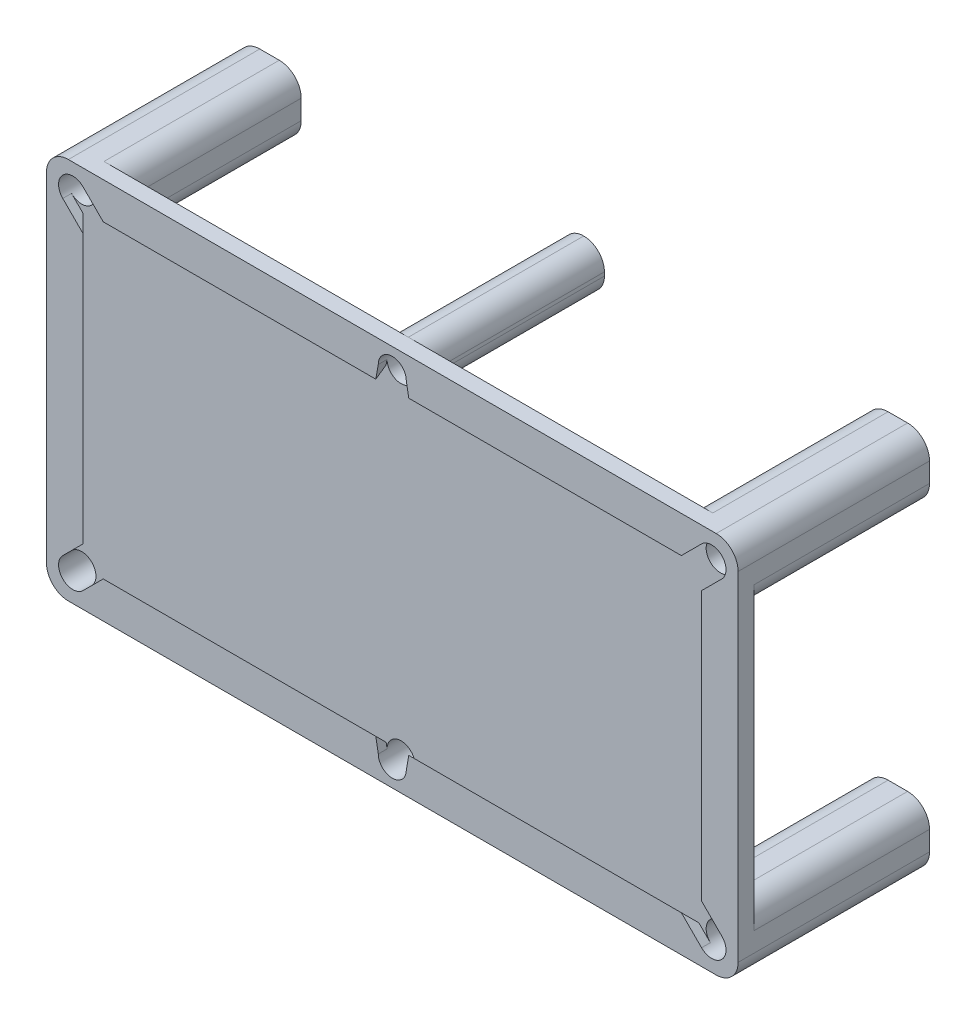
SolidWorks part; units mm, degrees
ref_plane "Płaszczyzna przednia" through (0, 0, 0) normal (0, 0, 1) x (1, 0, 0)
ref_plane "Płaszczyzna górna" through (0, 0, 0) normal (0, 1, 0) x (1, 0, 0)
ref_plane "Płaszczyzna prawa" through (0, 0, 0) normal (1, 0, 0) x (0, 0, -1)
sketch "Szkic1" plane through (0, 0, 0) normal (0, 0, 1) x (1, 0, 0)
  line L1 (-1420, -785) -> (1420, -785)
  line L2 (-1420, -785) -> (-1420, 785)
  line L3 (-1420, 785) -> (1420, 785)
  line L4 (1420, -785) -> (1420, 785)
  line L5 (-1420, -785) -> (1420, 785) construction
  line L6 (-1420, 785) -> (1420, -785) construction
  line L7 (-1270, -635) -> (1270, -635)
  line L8 (-1270, -635) -> (-1270, 635)
  line L9 (-1270, 635) -> (1270, 635)
  line L10 (1270, -635) -> (1270, 635)
  line L11 (-1270, -635) -> (1270, 635) construction
  line L12 (-1270, 635) -> (1270, -635) construction
  point P0 (0, 0)
  point P6 (0, 0)
  dimension "D1" = 2840
  dimension "D2" = 1570
  dimension "D3" = 2540
  dimension "D4" = 1270
extrude "Dodanie-wyciągnięcie1" add sketch "Szkic1" along normal blind 36
sketch "Szkic2" plane through (0, 0, 0) normal (0, 0, -1) x (-1, 0, 0)
  line L1 (-1420, -785) -> (1420, -785)
  line L2 (-1420, -785) -> (-1420, 785)
  line L3 (-1420, 785) -> (1420, 785)
  line L4 (1420, -785) -> (1420, 785)
  line L5 (-1420, -785) -> (1420, 785) construction
  line L6 (-1420, 785) -> (1420, -785) construction
  point P0 (0, 0)
chamfer "Sfazowanie1" distance 36 angle 45 4 edges at (-1270, 0, 0) (0, -635, 0) (1270, 0, 0) (0, 635, 0)
sketch "Szkic3" plane through (0, 0, 0) normal (0, 0, -1) x (-1, 0, 0)
  line L1 (-1420, -785) -> (1420, -785)
  line L2 (-1420, -785) -> (-1420, 785)
  line L3 (-1420, 785) -> (1420, 785)
  line L4 (1420, -785) -> (1420, 785)
  line L5 (-1420, -785) -> (1420, 785) construction
  line L6 (-1420, 785) -> (1420, -785) construction
  point P1 (0, 0)
extrude "Dodanie-wyciągnięcie3" add sketch "Szkic3" along normal blind 30
sketch "Szkic4" plane through (0, 0, 36) normal (0, 0, 1) x (1, 0, 0)
  line L0 (-1270, 635) -> (-1420, 785) construction
  line L1 (-1270, 635) -> (-1311.5425, 676.5425)
  line L2 (1270, 635) -> (1311.5425, 676.5425)
  line L3 (1270, -635) -> (1311.5425, -676.5425)
  line L4 (-1270, -635) -> (-1311.5425, -676.5425)
  line L5 (-1186.915, 635) -> (-1270, 718.085)
  line L7 (1270, 635) -> (1420, 785) construction
  line L8 (1270, -635) -> (1420, -785) construction
  line L9 (-1270, -635) -> (-1420, -785) construction
  line L10 (-1186.915, -635) -> (-1270, -718.085)
  line L11 (1270, 635) -> (-1270, 635) construction
  line L12 (-1270, 635) -> (-1270, -635) construction
  line L13 (-1270, -551.915) -> (-1353.085, -635)
  line L14 (-1270, -635) -> (1270, -635) construction
  line L17 (-1270, 551.915) -> (-1353.085, 635)
  line L18 (1186.915, 635) -> (1270, 718.085)
  line L19 (1270, 551.915) -> (1353.085, 635)
  line L20 (1270, -635) -> (1270, 635) construction
  line L21 (1270, -551.915) -> (1353.085, -635)
  line L22 (1186.915, -635) -> (1270, -718.085)
  circle A0 centre (-1311.5425, 676.5425) radius 58.75
  circle A1 centre (-1311.5425, -676.5425) radius 58.75
  circle A2 centre (1311.5425, -676.5425) radius 58.75
  circle A3 centre (1311.5425, 676.5425) radius 58.75
  point P0 (0, 0)
  line M12 (1270, 635) -> (1270, -635)
  line M13 (1270, -635) -> (-1270, -635)
  line M14 (-1270, -635) -> (-1270, 635)
  line M15 (-1270, 635) -> (1270, 635)
  dimension "D5" = 45
  dimension "D1" = 58.75
  dimension "D2" = 58.75
  dimension "D3" = 58.75
  dimension "D4" = 58.75
  dimension "D6" = 45
  dimension "D7" = 45
  dimension "D8" = 45
  dimension "D9" = 45
  dimension "D10" = 45
  dimension "D11" = 45
  dimension "D12" = 45
sketch "Szkic5" plane through (0, 0, -30) normal (0, 0, -1) x (-1, 0, 0)
  line L1 (-1420, 785) -> (-1160, 785)
  line L2 (-1420, 785) -> (-1420, 525)
  line L3 (-1420, 525) -> (-1160, 525)
  line L4 (-1160, 785) -> (-1160, 525)
  line L5 (1420, 785) -> (1160, 785)
  line L6 (1420, 785) -> (1420, 525)
  line L7 (1420, 525) -> (1160, 525)
  line L8 (1160, 785) -> (1160, 525)
  line L9 (1420, -785) -> (1160, -785)
  line L10 (1420, -785) -> (1420, -525)
  line L11 (1420, -525) -> (1160, -525)
  line L12 (1160, -785) -> (1160, -525)
  line L13 (-1420, -785) -> (-1160, -785)
  line L14 (-1420, -785) -> (-1420, -525)
  line L15 (-1420, -525) -> (-1160, -525)
  line L16 (-1160, -785) -> (-1160, -525)
  dimension "D1" = 260
  dimension "D2" = 260
  dimension "D3" = 260
  dimension "D4" = 260
  dimension "D5" = 260
  dimension "D6" = 260
  dimension "D7" = 260
  dimension "D8" = 260
extrude "Dodanie-wyciągnięcie4" add sketch "Szkic5" along normal blind 720
extrude "Wytnij-wyciągnięcie16" cut sketch "Szkic4" against normal blind 36 contours A1 | A1 L13 M14 | A1 L10 M13 | A0 | A0 L17 M14 | A0 L5 M15 | A3 | A3 L19 M12 | A3 L18 M15 | A2 | A2 L22 M13 | A2 L21 M12 region at (-1234.0308, 657.1646, 36) region at (-1258.7998, 698.3893, 36) region at (-1292.1646, 599.0308, 36) region at (1234.0308, 657.1646, 36) region at (1333.3893, 729.2852, 36) region at (1292.1646, 599.0308, 36) region at (-1292.1646, -599.0308, 36) region at (-1311.5425, -619.4542, 36) region at (-1234.0308, -657.1646, 36) region at (1292.1646, -599.0308, 36) region at (1364.2852, -654.6958, 36) region at (1234.0308, -657.1646, 36)
sketch "Szkic8" plane through (0, 0, 36) normal (0, 0, 1) x (1, 0, 0)
  circle A0 centre (-1311.5425, -676.5425) radius 58.75
  circle A1 centre (-1311.5425, 676.5425) radius 58.75
  circle A2 centre (1311.5425, 676.5425) radius 58.75
  circle A3 centre (1311.5425, -676.5425) radius 58.75
  dimension "D1" = 117.5
  dimension "D2" = 117.5
  dimension "D3" = 117.5
  dimension "D4" = 117.5
extrude "Wytnij-wyciągnięcie17" cut sketch "Szkic8" against normal blind 700
fillet "Zaokrąglenie1" radius 90 16 edges at (-1160, 525, -390) (-1160, -785, -390) (-1420, -785, -357) (-1160, -525, -390) (-1420, -525, -390) (-1420, 525, -390) (-1160, 785, -390) (-1420, 785, -357) (1160, -525, -390) (1420, -525, -390) (1420, -785, -357) (1160, -785, -390) (1160, 525, -390) (1420, 785, -357)
sketch "Szkic9" plane through (0, 0, 36) normal (0, 0, 1) x (1, 0, 0)
  line L0 (0, 785) -> (0, -785) construction
  line L1 (1420, 785) -> (-1420, 785) construction
  line L2 (1420, -785) -> (-1420, -785) construction
  line L3 (-1186.915, -635) -> (1186.915, -635) construction
  line L4 (1186.915, 635) -> (-1186.915, 635) construction
  line L5 (-57.5, 692.5) -> (-67.6388, 635)
  line L6 (57.5, 692.5) -> (67.6388, 635)
  line L7 (-57.5, -692.5) -> (-67.6388, -635)
  line L8 (57.5, -692.5) -> (67.6388, -635)
  circle A0 centre (0, 692.5) radius 57.5
  circle A1 centre (0, -692.5) radius 57.5
  line M3 (1186.915, -635) -> (-1186.915, -635)
  line M11 (-1186.915, 635) -> (1186.915, 635)
  dimension "D3" = 115
  dimension "D4" = 115
  dimension "D1" = 57.5
  dimension "D2" = 57.5
  dimension "D5" = 80
  dimension "D6" = 80
  dimension "D7" = 80
  dimension "D8" = 80
extrude "Wytnij-wyciągnięcie18" cut sketch "Szkic9" against normal blind 36 contours A0 L5 M11 | L0 A0 | A0 L0 | A0 L6 M11 | A1 L7 M3 | L0 A1 | A1 L0 | A1 L8 M3 region at (24.4038, 692.5, 36) region at (49.3805, -649.6849, 36) region at (24.4038, -692.5, 36) region at (-24.4038, -692.5, 36) region at (-49.3805, -649.6849, 36) region at (-24.4038, 692.5, 36) region at (-49.3805, 649.6849, 36) region at (49.3805, 649.6849, 36)
sketch "Szkic10" plane through (0, 0, 36) normal (0, 0, 1) x (1, 0, 0)
  circle A0 centre (0, 692.5) radius 57.5
  circle A1 centre (0, -692.5) radius 57.5
  dimension "D1" = 115
  dimension "D2" = 115
sketch "Szkic11" plane through (0, 0, -30) normal (0, 0, -1) x (-1, 0, 0)
  line L0 (-1420, 785) -> (1420, 785) construction
  line L1 (-85, 600) -> (85, 600)
  line L2 (-85, 600) -> (-85, 785)
  line L3 (-85, 785) -> (85, 785)
  line L4 (85, 600) -> (85, 785)
  line L5 (-85, 600) -> (85, 785) construction
  line L6 (-85, 785) -> (85, 600) construction
  line L7 (-1420, -785) -> (1420, -785) construction
  line L8 (-85, -600) -> (85, -600)
  line L9 (-85, -600) -> (-85, -785)
  line L10 (-85, -785) -> (85, -785)
  line L11 (85, -600) -> (85, -785)
  line L12 (-85, -600) -> (85, -785) construction
  line L13 (-85, -785) -> (85, -600) construction
  point P0 (0, 692.5)
  point P8 (0, -692.5)
  dimension "D1" = 170
  dimension "D2" = 170
extrude "Dodanie-wyciągnięcie5" add sketch "Szkic11" along normal blind 720
fillet "Zaokrąglenie2" radius 85 8 edges at (85, -785, -390) (85, -600, -390) (-85, -600, -390) (-85, -785, -390) (-85, 600, -390) (85, 600, -390) (85, 785, -390) (-85, 785, -390)
extrude "Wytnij-wyciągnięcie19" cut sketch "Szkic10" against normal blind 700
